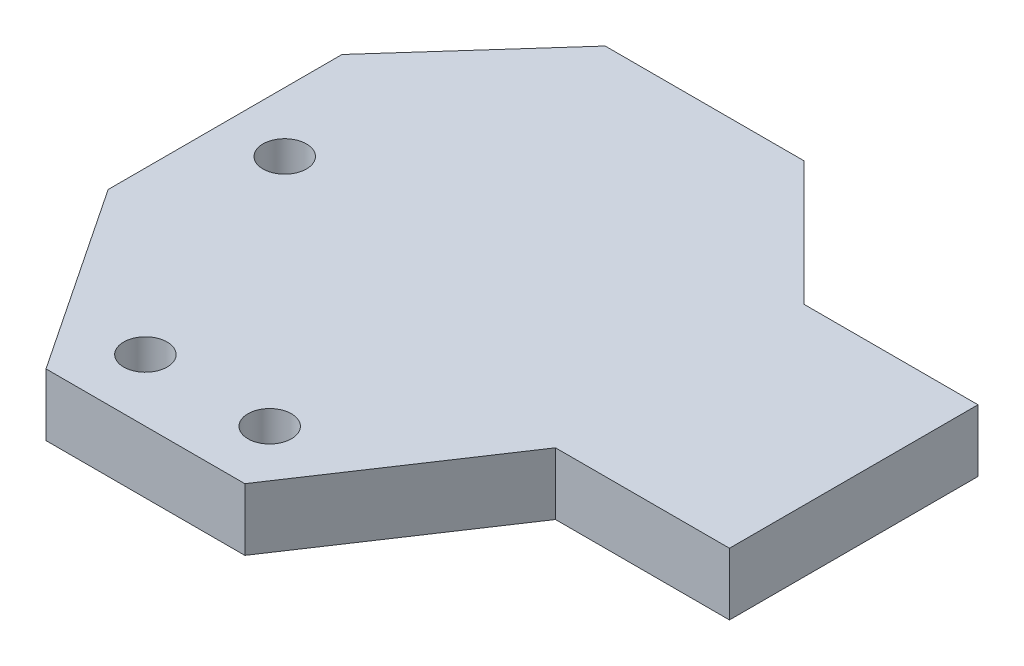
SolidWorks part; units mm, degrees
ref_plane "Front Plane" through (0, 0, 0) normal (0, 0, 1) x (1, 0, 0)
ref_plane "Top Plane" through (0, 0, 0) normal (0, 1, 0) x (1, 0, 0)
ref_plane "Right Plane" through (0, 0, 0) normal (1, 0, 0) x (0, 0, -1)
sketch "Sketch1" plane through (0, 0, 0) normal (0, 1, 0) x (1, 0, 0)
  line L0 (0, 33.8197) -> (10, 45)
  line L1 (0, 0) -> (50, 0)
  line L2 (0, 0) -> (0, 45)
  line L3 (0, 45) -> (50, 45)
  line L4 (50, 0) -> (50, 45)
  line L5 (0, 15) -> (10, 0)
  line L6 (26, 45) -> (36, 35)
  line L7 (26, 0) -> (36, 15)
  line L8 (36, 15) -> (50, 15)
  line L9 (36, 35) -> (50, 35)
  line L10 (50, 25) -> (0, 25) construction
  circle A1 centre (13, 5) radius 1.75
  circle A2 centre (23, 5) radius 1.75
  point P23 (0, 0)
  dimension "D15" = 10
  dimension "D16" = 3.5
  dimension "D24" = 3
  dimension "D25" = 3
  dimension "D17" = 3.5
  dimension "D1" = 45
  dimension "D2" = 50
  dimension "D3" = 15
  dimension "D4" = 10
  dimension "D5" = 10
  dimension "D6" = 15
  dimension "D7" = 16
  dimension "D8" = 16
  dimension "D9" = 10
  dimension "D10" = 10
  dimension "D11" = 10
  dimension "D12" = 20
  dimension "D13" = 10
  dimension "D18" = 5
extrude "Boss-Extrude1" add sketch "Sketch1" along normal blind 5 contours L4 L10 L2 L5 L1 L7 L8 | L10 L4 L9 L6 L3 L0 L2 | L10 | L10 region at (22.3613, 0, -23.5179)
ref_plane "Plane1" through (0, 0, 0) normal (0, -1, 0) x (-1, 0, 0)
sketch "Sketch2" plane through (0, 0, 0) normal (0, -1, 0) x (-1, 0, 0)
  line L0 (0, 24.4098) -> (-68.9029, 24.4098) construction
  line L1 (0, 15) -> (0, 33.8197) construction
  circle A0 centre (-4.8, 24.4098) radius 1.75
  dimension "D1" = 4.8
extrude "Cut-Extrude1" cut sketch "Sketch2" against normal blind 10 contours A0
